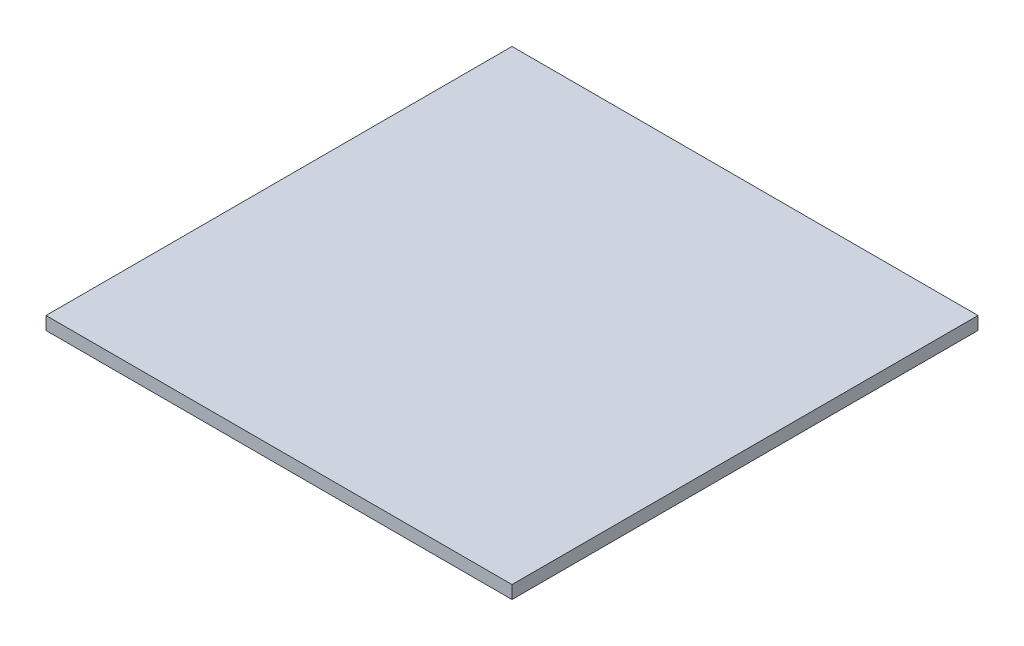
SolidWorks part; units mm, degrees
material "ABS"
ref_plane "Front (1)" through (0, 0, 0) normal (0, 0, 1) x (1, 0, 0)
ref_plane "Top (2)" through (0, 0, 0) normal (0, 1, 0) x (1, 0, 0)
ref_plane "Right (3)" through (0, 0, 0) normal (1, 0, 0) x (0, 0, -1)
ref_axis "X Axis" through (13.5064, 0, 0) along (-1, 0, 0)
ref_axis "Y Axis" through (0, 12.3593, 0) along (0, -1, 0)
ref_axis "Z Axis" through (0, 0, 14.1119) along (0, 0, -1)
sketch "Sketch1" plane through (0, 0, 0) normal (0, 1, 0) x (0, 0, -1)
  line L0 (146.0532, 148) -> (114.9532, 148) construction
  line L1 (-42.2484, -33.5) -> (172.7516, -33.5)
  line L2 (-42.2484, -33.5) -> (-42.2484, 181.5)
  line L3 (-42.2484, 181.5) -> (172.7516, 181.5)
  line L4 (172.7516, -33.5) -> (172.7516, 181.5)
  line L5 (15.55, 0) -> (-15.55, 0) construction
  line L6 (0, 0) -> (130.5032, 148) construction
  line L7 (-42.2484, 181.5) -> (172.7516, -33.5) construction
  line L8 (146.0532, 148) -> (146.0532, 0) construction
  line L9 (-23.35, 148) -> (358.8532, 148) construction
  point P10 (65.2516, 74)
  dimension "D1" = 215
extrude "Boss-Extrude1" add sketch "Sketch1" along normal blind 6
